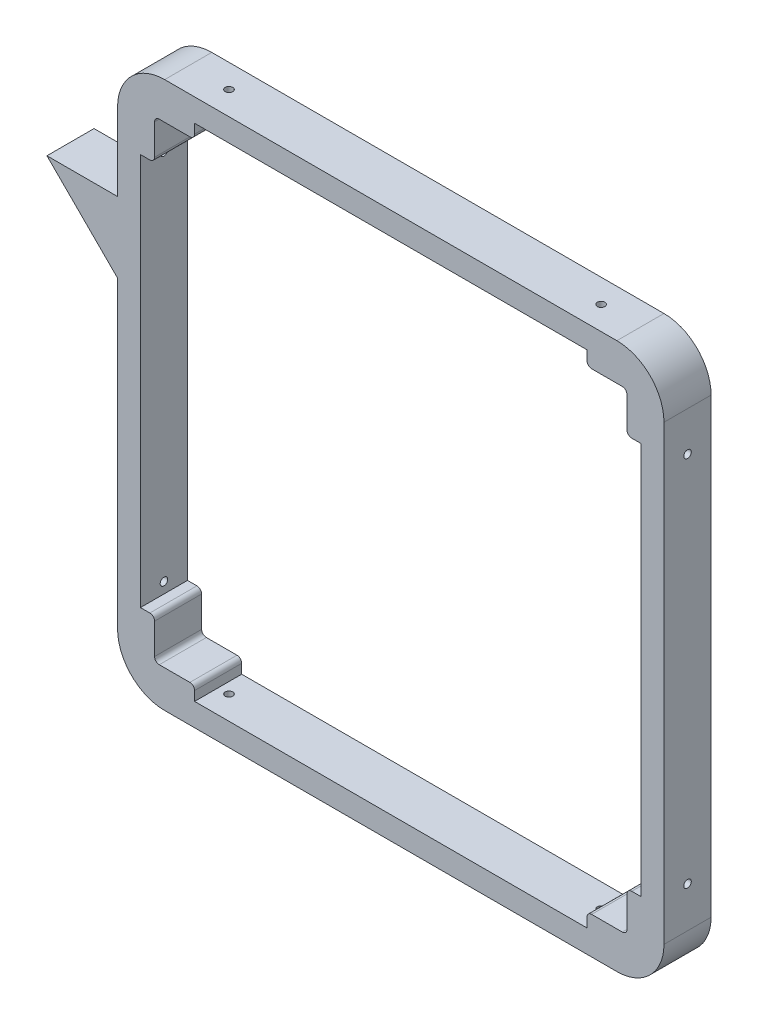
SolidWorks part; units mm, degrees
material "Nylon 101"
ref_plane "Front Plane" through (0, 0, 0) normal (0, 0, 1) x (1, 0, 0)
ref_plane "Top Plane" through (0, 0, 0) normal (0, 1, 0) x (1, 0, 0)
ref_plane "Right Plane" through (0, 0, 0) normal (1, 0, 0) x (0, 0, -1)
sketch "Sketch1" plane through (0, 0, 0) normal (0, 0, 1) x (1, 0, 0)
  line L13 (50.0019, -50.0019) -> (58, -58) construction
  line L14 (53, -41.5) -> (50.0019, -41.5)
  line L17 (41.5, -53) -> (41.5, -50.0019)
  line L18 (50.0019, -44.9586) -> (53, -44.9586)
  line L20 (53, -44.9586) -> (53, -53)
  line L23 (53, -53) -> (44.9586, -53)
  line L24 (44.9586, -53) -> (44.9586, -50.0019)
  line L25 (50.0019, -41.5) -> (50.0019, -50.0019)
  line L27 (50.0019, -50.0019) -> (41.5, -50.0019)
  line L35 (-41.5, 53) -> (41.5, 53)
  line L37 (50.0019, -50.0019) -> (50.0019, -41.5)
  line L38 (41.5, -50.0019) -> (50.0019, -50.0019)
  line L39 (53, -44.9586) -> (50.0019, -44.9586)
  line L40 (53, -53) -> (53, -44.9586)
  line L42 (44.9586, -53) -> (53, -53)
  line L43 (44.9586, -50.0019) -> (44.9586, -53)
  line L44 (53, -41.5) -> (50.0019, -41.5)
  line L45 (41.5, -53) -> (41.5, -50.0019)
  line L47 (53, -41.5) -> (53, 41.5)
  line L50 (41.5, -53) -> (-41.5, -53)
  line L52 (-41.5, -53) -> (-41.5, -50.0019)
  line L53 (-53, -41.5) -> (-50.0019, -41.5)
  line L54 (-44.96, -50.0019) -> (-44.96, -53)
  line L55 (-44.96, -53) -> (-53, -53)
  line L57 (-53, -53) -> (-53, -44.96)
  line L58 (-53, -44.96) -> (-50.0019, -44.96)
  line L59 (-41.5, -50.0019) -> (-50.0019, -50.0019)
  line L60 (-50.0019, -50.0019) -> (-50.0019, -41.5)
  line L61 (-53, -41.5) -> (-53, 41.5)
  line L63 (58, 58) -> (58, -58)
  line L65 (-50.0019, -50.0019) -> (-41.5, -50.0019)
  line L66 (-50.0019, -41.5) -> (-50.0019, -50.0019)
  line L67 (-44.96, -53) -> (-44.96, -50.0019)
  line L68 (-53, -53) -> (-44.96, -53)
  line L70 (-53, -44.96) -> (-53, -53)
  line L71 (-50.0019, -44.96) -> (-53, -44.96)
  line L72 (-41.5, -53) -> (-41.5, -50.0019)
  line L73 (-53, -41.5) -> (-50.0019, -41.5)
  line L75 (58, -58) -> (-58, -58)
  line L77 (-50.0019, -50.0019) -> (-58, -58) construction
  line L79 (-58, -58) -> (-58, 58)
  line L81 (-53, 41.5) -> (-50.0019, 41.5)
  line L82 (-41.5, 53) -> (-41.5, 50.0019)
  line L83 (-50.0019, 44.96) -> (-53, 44.96)
  line L84 (-53, 44.96) -> (-53, 53)
  line L86 (-53, 53) -> (-44.96, 53)
  line L87 (-44.96, 53) -> (-44.96, 50.0019)
  line L88 (-50.0019, 41.5) -> (-50.0019, 50.0019)
  line L89 (-50.0019, 50.0019) -> (-41.5, 50.0019)
  line L90 (-58, 58) -> (58, 58)
  line L94 (-50.0019, 50.0019) -> (-50.0019, 41.5)
  line L95 (-41.5, 50.0019) -> (-50.0019, 50.0019)
  line L96 (-53, 44.96) -> (-50.0019, 44.96)
  line L97 (-53, 53) -> (-53, 44.96)
  line L99 (-44.96, 53) -> (-53, 53)
  line L100 (-44.96, 50.0019) -> (-44.96, 53)
  line L101 (-53, 41.5) -> (-50.0019, 41.5)
  line L102 (-41.5, 53) -> (-41.5, 50.0019)
  line L106 (-50.0019, 50.0019) -> (-58, 58) construction
  line L110 (41.5, 53) -> (41.5, 50.0019)
  line L111 (53, 41.5) -> (50.0019, 41.5)
  line L112 (44.9586, 50.0019) -> (44.9586, 53)
  line L113 (44.9586, 53) -> (53, 53)
  line L115 (53, 53) -> (53, 44.96)
  line L116 (53, 44.96) -> (50.0019, 44.96)
  line L117 (41.5, 50.0019) -> (50.0019, 50.0019)
  line L118 (50.0019, 50.0019) -> (50.0019, 41.5)
  line L123 (50.0019, 50.0019) -> (41.5, 50.0019)
  line L124 (50.0019, 41.5) -> (50.0019, 50.0019)
  line L125 (44.9586, 53) -> (44.9586, 50.0019)
  line L126 (53, 53) -> (44.9586, 53)
  line L128 (53, 44.96) -> (53, 53)
  line L129 (50.0019, 44.96) -> (53, 44.96)
  line L130 (41.5, 53) -> (41.5, 50.0019)
  line L131 (53, 41.5) -> (50.0019, 41.5)
  line L135 (50.0019, 50.0019) -> (58, 58) construction
  point P2 (0, 58)
  point P4 (0, 53)
  point P6 (0, -53)
  point P7 (0, -58)
  point P10 (53, 0)
  point P11 (-53, 0)
  point P16 (-58, 0)
  point P17 (58, 0)
  dimension "D1" = 106
  dimension "D2" = 5
  dimension "D3" = 2.9981
extrude "base" add sketch "Sketch1" along normal mid plane 10 contours L20 L13 L14 L25 L18 | L13 L23 L24 L27 L17 | L13 L27 L24 L23 | L25 L13 L20 L18 | L117 L118 L116 L115 L113 L112 | L88 L89 L87 L86 L84 L83 | L59 L60 L58 L57 L55 L54 region at (51.5009, -45.0723, 0) region at (50.1156, 47.4809, 0) region at (-45.0737, -51.5009, 0) region at (-47.4809, 50.1156, 0) region at (56.3595, 0, 0)
ref_plane "Plane3" through (0, 0, 15) normal (0, 0, 1) x (1, 0, 0)
sketch "Sketch7" plane through (0, 0, 15) normal (0, 0, 1) x (1, 0, 0)
  line L0 (-41.65, 53.15) -> (41.65, 53.15)
  line L1 (41.65, 53.15) -> (41.65, 50.1519)
  line L2 (41.65, 50.1519) -> (50.1519, 50.1519)
  line L3 (50.1519, 50.1519) -> (50.1519, 41.65)
  line L4 (50.1519, 41.65) -> (53.15, 41.65)
  line L5 (53.15, 41.65) -> (53.15, -41.65)
  line L6 (53.15, -41.65) -> (50.1519, -41.65)
  line L7 (50.1519, -41.65) -> (50.1519, -50.1519)
  line L8 (50.1519, -50.1519) -> (41.65, -50.1519)
  line L9 (41.65, -50.1519) -> (41.65, -53.15)
  line L10 (41.65, -53.15) -> (-41.65, -53.15)
  line L11 (-41.65, -53.15) -> (-41.65, -50.1519)
  line L12 (-41.65, -50.1519) -> (-50.1519, -50.1519)
  line L13 (-50.1519, -50.1519) -> (-50.1519, -41.65)
  line L14 (-50.1519, -41.65) -> (-53.15, -41.65)
  line L15 (-53.15, -41.65) -> (-53.15, 41.65)
  line L16 (-53.15, 41.65) -> (-50.1519, 41.65)
  line L17 (-50.1519, 41.65) -> (-50.1519, 50.1519)
  line L18 (-50.1519, 50.1519) -> (-41.65, 50.1519)
  line L19 (-41.65, 50.1519) -> (-41.65, 53.15)
  line L21 (-41.5, 53) -> (41.5, 53) construction
  line L22 (-41.5, 53) -> (-41.5, 50.0019) construction
  line L23 (-50.0019, 50.0019) -> (-41.5, 50.0019) construction
  line L24 (-50.0019, 41.5) -> (-50.0019, 50.0019) construction
  line L25 (-53, 41.5) -> (-50.0019, 41.5) construction
  line L26 (-53, -41.5) -> (-53, 41.5) construction
  line L27 (-53, -41.5) -> (-50.0019, -41.5) construction
  line L28 (-50.0019, -50.0019) -> (-50.0019, -41.5) construction
  line L29 (-41.5, -50.0019) -> (-50.0019, -50.0019) construction
  line L30 (-41.5, -53) -> (-41.5, -50.0019) construction
  line L31 (41.5, -53) -> (-41.5, -53) construction
  line L32 (41.5, -53) -> (41.5, -50.0019) construction
  line L33 (50.0019, -41.5) -> (50.0019, -50.0019) construction
  line L34 (53, -41.5) -> (53, 41.5) construction
  line L35 (50.0019, 50.0019) -> (50.0019, 41.5) construction
  line L36 (53, 41.5) -> (50.0019, 41.5) construction
  line L37 (41.5, 50.0019) -> (50.0019, 50.0019) construction
  dimension "D1" = 0.15
  dimension "D2" = 0.15
  dimension "D3" = 0.15
  dimension "D4" = 0.15
  dimension "D5" = 0.15
  dimension "D6" = 0.15
  dimension "D7" = 0.15
  dimension "D8" = 0.15
  dimension "D9" = 0.15
  dimension "D10" = 0.15
  dimension "D11" = 0.15
  dimension "D12" = 0.15
  dimension "D13" = 0.15
  dimension "D14" = 0.15
  dimension "D15" = 0.15
  dimension "D16" = 0.15
  dimension "D17" = 0.15
ref_plane "arm plane" through (0, 0, 0) normal (0.7071, 0.7071, 0) x (0.7071, -0.7071, 0)
sketch "Sketch2" plane through (0, 0, 0) normal (0.7071, 0.7071, 0) x (0.7071, -0.7071, 0)
  line L4 (70.9255, 5) -> (82.0244, 5)
  line L6 (66.8216, 5) -> (8.1317, 5) construction
  line L8 (82.0244, 5) -> (82.0244, 23.31)
  line L9 (82.0244, 23.31) -> (5.0244, 23.31)
  line L12 (5.0244, 23.31) -> (16.3344, 12)
  line L13 (16.3344, 12) -> (70.9255, 12)
  line L14 (70.9255, 12) -> (70.9255, 5)
  dimension "D1" = 45
  dimension "D2" = 11.31
  dimension "D3" = 77
  dimension "D4" = 7
extrude "arm" add sketch "Sketch2" along normal mid plane 10
sketch "Sketch3" plane through (0, 0, 0) normal (0, 0, 1) x (1, 0, 0)
  line L1 (61.5355, -54.4645) -> (54.4645, -61.5355) construction
  line L6 (58, 58) -> (58, -50.9289) construction
  line L7 (50.9289, -58) -> (-58, -58) construction
  line L8 (8.0146, -15.0857) -> (46.6163, -53.6874) construction
  line L9 (58, -50.9289) -> (61.5355, -54.4645) construction
  line L10 (54.818, -61.8891) -> (61.8891, -54.818)
  line L11 (61.8891, -54.818) -> (58, -50.9289)
  line L12 (58, -50.9289) -> (58, -58)
  line L13 (58, -58) -> (50.9289, -58)
  line L14 (50.9289, -58) -> (54.818, -61.8891)
  dimension "D1" = 0.5
extrude "Cut-Extrude1" cut sketch "Sketch3" against normal through all
ref_plane "Plane2" through (0, 0, -5) normal (0, 0, -1) x (-1, 0, 0)
sketch "Sketch5" plane through (0, 0, -5) normal (0, 0, -1) x (-1, 0, 0)
  line L0 (-46.6163, -53.6874) -> (-43.0808, -50.1519)
  line L7 (-50.1519, -43.0808) -> (-53.6874, -46.6163)
  line L8 (-53.6874, -46.6163) -> (-53.6874, -53.6874)
  line L9 (-50.0019, -50.0019) -> (-58, -58) construction
  line L10 (-53.6874, -53.6874) -> (-46.6163, -53.6874)
  line L12 (-53.6874, -46.6163) -> (-58, -50.9289) construction
  line L14 (-50.1519, -41.65) -> (-50.1519, -50.1519) construction
  line L15 (-50.1519, -50.1519) -> (-41.65, -50.1519) construction
  line L16 (-50.1519, -43.0808) -> (-50.1519, -50.1519)
  line L17 (-50.1519, -50.1519) -> (-43.0808, -50.1519)
  dimension "D1" = 5
  dimension "D2" = 10
extrude "Boss-Extrude4" add sketch "Sketch5" along normal up to surface (7 mm away) contours L8 L10 L0 L7 | L7 L8 L10 L0 L17 L16 region at (50.1519, -53.5374, -5) up to face at (30.851, -30.851, -12)
ref_plane "Mirror Plane" through (10.0177, -10.0177, -14.1672) normal (-0.5, 0.5, 0.7071) x (0.866, 0.2887, 0.4082)
sketch "Sketch9" plane through (10.0177, -10.0177, -14.1672) normal (-0.5, 0.5, 0.7071) x (0.866, 0.2887, 0.4082)
  line L0 (-9.2532, -10.2967) -> (12.7922, 5.2918)
  line L1 (-30.6152, 19.9137) -> (12.7922, 5.2918) construction
  line L2 (5.852, 0.3843) -> (-2.313, -5.3892) construction
  line L3 (-9.2532, -10.2967) -> (-30.6152, 19.9137)
  line L4 (-30.6152, 19.9137) -> (-8.5698, 35.5021)
  line L5 (-8.5698, 35.5021) -> (12.7922, 5.2918)
  line L6 (-8.5698, 35.5021) -> (-9.2532, -10.2967) construction
  line L7 (-8.8089, 34.1083) -> (-29.2213, 19.6745)
  line L8 (-29.2213, 19.6745) -> (-9.0141, -8.9028)
  line L9 (-9.0141, -8.9028) -> (11.3984, 5.5309)
  line L10 (11.3984, 5.5309) -> (-8.8089, 34.1083)
  line L11 (-9.0141, -8.9028) -> (-8.8089, 34.1083) construction
  line L12 (-29.2213, 19.6745) -> (11.3984, 5.5309) construction
  point P4 (1.7695, -2.5025)
  point P5 (1.7695, -2.5025)
  point P12 (-8.9115, 12.6027)
  point P13 (-8.9115, 12.6027)
  dimension "D1" = 27
  dimension "D2" = 37
  dimension "D3" = 1
  dimension "D4" = 1
extrude "Boss-Extrude5" add sketch "Sketch9" along normal blind 4
extrude "Boss-Extrude6" add sketch "Sketch9<2>" along normal blind 1 contours L9 L10 L7 L8 region at (2.3002, -2.3002, -25.0815)
sketch "Sketch9<2>" plane through (10.0177, -10.0177, -14.1672) normal (-0.5, 0.5, 0.7071) x (0.866, 0.2887, 0.4082) same geometry as "Sketch9"
extrude "clearance" cut sketch "Sketch7" against normal up to surface (20 mm away) up to face at (0, 0, -5)
sketch "Sketch10" plane through (0, 0, 0) normal (0, 1, 0) x (1, 0, 0)
  line L0 (41.65, 5) -> (41.65, -5) construction
  circle A0 centre (39.65, 0) radius 0.8
  circle A1 centre (-39.35, 0) radius 0.8
  point P5 (41.65, 0)
  dimension "D1" = 1.6
  dimension "D2" = 2
  dimension "D3" = 79
hole_wizard "M2x0.4 Tapped Hole1" positions "Sketch11" profile "Sketch12" tap size "M2x0.4" standard "ANSI Metric" end condition through all
sketch "Sketch11" plane through (0, 0, 0) normal (0, 1, 0) x (1, 0, 0)
  point P0 (-39.35, 0)
  point P2 (39.65, 0)
sketch "Sketch12" plane through (-39.35, 0, 0) normal (1, 0, 0) x (0, 0, -1)
  line L0 (0, 0) -> (0, 58)
  line L1 (0, 58) -> (0.8, 58)
  line L2 (0.8, 58) -> (0.8, 0)
  line L5 (0.8, 0) -> (0, 0)
  line L11 (0, -6.35) -> (0, 107.95) construction
  dimension "Thru Tap Drill Dia." = 1.6
  dimension "Thru Tap Drill Depth" = 58
cosmetic thread "Hole Thread1" parameters "D2"=2
cosmetic thread "Hole Thread2" parameters "D2"=2
mirror "Mirror1" about plane through (0, 0, 0) normal (0, 1, 0) of "M2x0.4 Tapped Hole1"
cosmetic thread "Hole Thread3" parameters "D2"=2
cosmetic thread "Hole Thread4" parameters "D2"=2
sketch "Sketch13" plane through (0, 0, 0) normal (1, 0, 0) x (0, 0, -1)
  line L2 (5, 41.65) -> (-5, 41.65) construction
  circle A0 centre (0, 39.65) radius 0.8
  circle A1 centre (0, -39.35) radius 0.8
  dimension "D1" = 1.6
  dimension "D3" = 79
  dimension "D2" = 2
hole_wizard "M2x0.4 Tapped Hole2" positions "Sketch14" profile "Sketch15" tap size "M2x0.4" standard "ANSI Metric" end condition through all
sketch "Sketch14" plane through (0, 0, 0) normal (1, 0, 0) x (0, 0, -1)
  point P0 (0, 39.65)
  point P3 (0, -39.35)
sketch "Sketch15" plane through (0, 39.65, 0) normal (0, 1, 0) x (0, 0, 1)
  line L0 (0, 0) -> (0, 58)
  line L1 (0, 58) -> (0.8, 58)
  line L2 (0.8, 58) -> (0.8, 0)
  line L5 (0.8, 0) -> (0, 0)
  line L11 (0, -6.35) -> (0, 107.95) construction
  dimension "Thru Tap Drill Dia." = 1.6
  dimension "Thru Tap Drill Depth" = 58
cosmetic thread "Hole Thread5" parameters "D2"=2
cosmetic thread "Hole Thread6" parameters "D2"=2
mirror "Mirror2" about plane through (0, 0, 0) normal (1, 0, 0) of "M2x0.4 Tapped Hole2"
cosmetic thread "Hole Thread7" parameters "D2"=2
cosmetic thread "Hole Thread8" parameters "D2"=2
sketch "Sketch16" plane through (0, 0, -5) normal (0, 0, -1) x (-1, 0, 0)
  line L5 (53.15, 21.65) -> (109.7185, 78.2185)
  line L6 (53.15, -41.65) -> (53.15, 41.65) construction
  line L8 (109.7185, 78.2185) -> (109.7185, 68.2185)
  line L10 (-58, -58) -> (58, 58) construction
  line L18 (109.7185, 68.2185) -> (53.15, 11.65)
  line L19 (53.15, 11.65) -> (53.15, 21.65)
  dimension "D1" = 80
  dimension "D2" = 10
  dimension "D3" = 20
extrude "extender" add sketch "Sketch16" along normal blind 18.31 contours L19 L18 L8 L5 region at (-81.4343, 44.9343, -5)
ref_plane "Plane5" through (-15.75, -15.75, 0) normal (0.7071, 0.7071, 0) x (0.7071, -0.7071, 0)
sketch "Sketch17" plane through (-15.75, -15.75, 0) normal (0.7071, 0.7071, 0) x (0.7071, -0.7071, 0)
  line L0 (-132.8916, 23.31) -> (-132.8916, 5)
  line L1 (-121.5816, 12) -> (-110.2716, 23.31)
  line L3 (-110.2716, 23.31) -> (-132.8916, 23.31)
  line L5 (-59.7505, 5) -> (-132.8916, 5) construction
  line L6 (-52.8916, 23.31) -> (-132.8916, 23.31) construction
  line L7 (-121.5816, 12) -> (-121.5816, 5)
  line L8 (-121.5816, 5) -> (-132.8916, 5)
  dimension "D1" = 45
  dimension "D2" = 7
  dimension "D3" = 11.31
extrude "angled horizontal" add sketch "Sketch17" along normal up to vertex (30.4056 mm away) up to point (-41.65, 53.15, -5)
ref_plane "Plane7" through (-47.2282, 47.2282, -66.7908) normal (0.5, -0.5, 0.7071) x (0.866, 0.2887, -0.4082)
sketch "Sketch19" plane through (-47.2282, 47.2282, -66.7908) normal (0.5, -0.5, 0.7071) x (0.866, 0.2887, -0.4082)
  line L0 (-55.7578, 55.4737) -> (-34.3958, 25.2634)
  line L1 (-38.097, 67.9618) -> (-62.923, 50.4071) construction
  line L2 (-38.097, 67.9618) -> (-28.8624, 54.9022) construction
  line L5 (-55.7578, 55.4737) -> (-33.7124, 71.0622)
  line L6 (-33.7124, 71.0622) -> (-12.3504, 40.8518)
  line L7 (-12.3504, 40.8518) -> (-34.3958, 25.2634)
  line L8 (-55.7578, 55.4737) -> (-12.3504, 40.8518) construction
  line L9 (-33.7124, 71.0622) -> (-34.3958, 25.2634) construction
  line L10 (-54.3639, 55.2346) -> (-33.9515, 69.6683)
  line L11 (-33.9515, 69.6683) -> (-13.7443, 41.091)
  line L12 (-13.7443, 41.091) -> (-34.1567, 26.6572)
  line L13 (-34.1567, 26.6572) -> (-54.3639, 55.2346)
  line L14 (-54.3639, 55.2346) -> (-13.7443, 41.091) construction
  line L15 (-33.9515, 69.6683) -> (-34.1567, 26.6572) construction
  dimension "D1" = 21.63
  dimension "D2" = 37
  dimension "D3" = 27
  dimension "D4" = 1
  dimension "D5" = 1
  dimension "D6" = 1
  dimension "D7" = 1
extrude "Boss-Extrude9" add sketch "Sketch19" along normal blind 4
extrude "Boss-Extrude10" add sketch "Sketch19<2>" along normal blind 1 contours L13 L12 L11 L10 region at (-76.7199, 76.7224, -25.0815)
sketch "Sketch19<2>" plane through (-47.2282, 47.2282, -66.7908) normal (0.5, -0.5, 0.7071) x (0.866, 0.2887, -0.4082) same geometry as "Sketch19"
sketch "Sketch21" plane through (0, 0, 0) normal (0, 0, 1) x (1, 0, 0)
  line L0 (-58, 16.5) -> (-58, 31.5)
  line L1 (-73, 31.5) -> (-58, 31.5)
  line L2 (-73, 31.5) -> (-58, 16.5)
  line L6 (-109.7185, 68.2185) -> (-58, 16.5) construction
  line L7 (-58, -58) -> (-58, 58) construction
  dimension "D2" = 15
extrude "Boss-Extrude11" add sketch "Sketch21" along normal up to surface (5 mm away) and the other way up to surface (5 mm away) up to face at (0, 0, 5) other way up to face at (-86.514, 64.4426, -5)
fillet "Fillet1" radius 1 12 edges at (50.1519, -41.65, 0) (41.65, -50.1519, 0) (-50.1519, -41.65, 0) (-41.65, -50.1519, 0) (-50.1519, 41.65, 0) (-41.65, 50.1519, 0) (41.65, 50.1519, 0) (50.1519, 41.65, 0) (50.1519, 50.1519, 0) (50.1519, -50.1519, -3.5) (-50.1519, -50.1519, 0) (-50.1519, 50.1519, 0)
fillet "Fillet2" radius 10 4 edges at (58, -58, -9.155) (58, 58, 0) (-58, 58, 0) (-58, -58, 0)
split "Split1" bodies to split 125 resulting bodies 128 split by face at (5.0342, 27.3231, -5)
